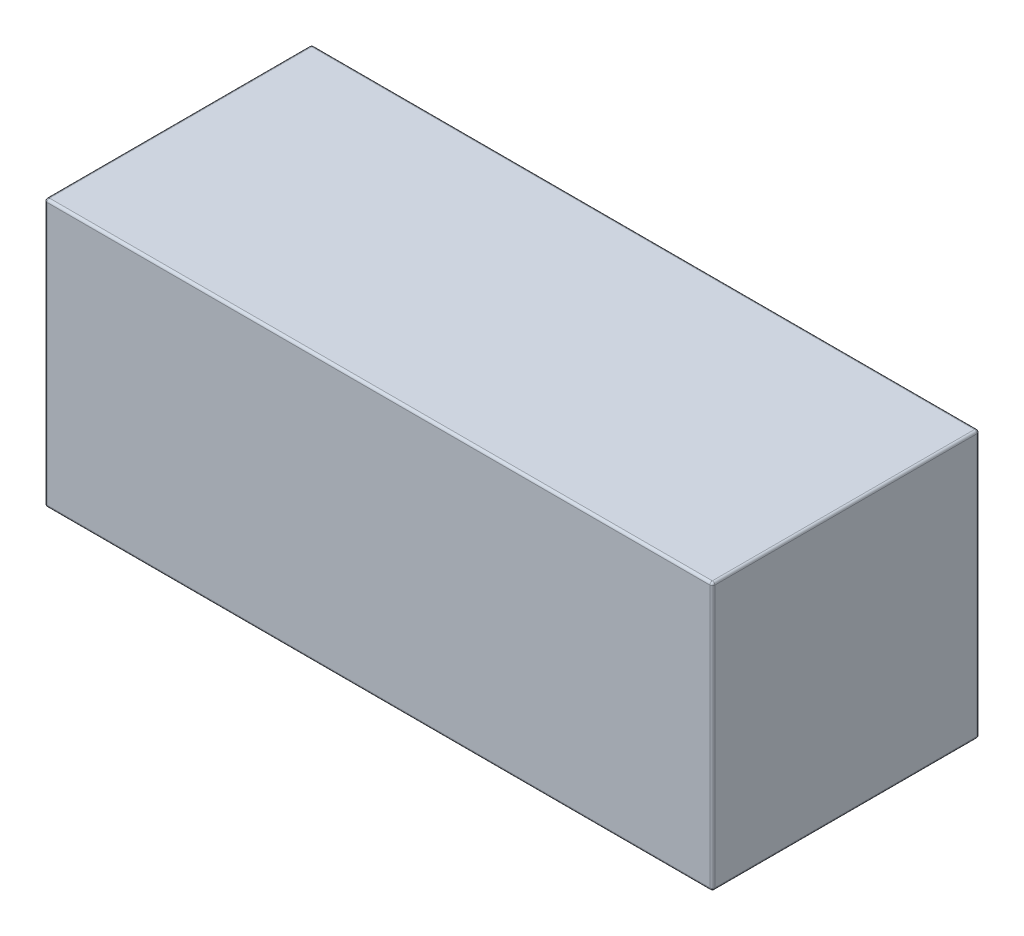
SolidWorks part; units mm, degrees
ref_plane "Plan de face" through (0, 0, 0) normal (0, 0, 1) x (1, 0, 0)
ref_plane "Plan de dessus" through (0, 0, 0) normal (0, 1, 0) x (1, 0, 0)
ref_plane "Plan de droite" through (0, 0, 0) normal (1, 0, 0) x (0, 0, -1)
sketch "Esquisse1" plane through (0, 0, 0) normal (0, 0, 1) x (1, 0, 0)
  line L1 (0, 0) -> (135, 0)
  line L2 (0, 0) -> (0, -54)
  line L3 (0, -54) -> (135, -54)
  line L4 (135, 0) -> (135, -54)
  dimension "D1" = 135
  dimension "D2" = 54
extrude "Boss.-Extru.1" add sketch "Esquisse1" along normal blind 54
sketch "Esquisse2" plane through (0, -54, 0) normal (0, -1, 0) x (1, 0, 0)
  line L0 (135, 54) -> (135, 0) construction
  line L1 (62.25, 51) -> (72.75, 51)
  line L2 (62.25, 51) -> (62.25, 40.5)
  line L3 (62.25, 40.5) -> (72.75, 40.5)
  line L4 (72.75, 51) -> (72.75, 40.5)
  line L5 (0, 54) -> (135, 54) construction
  line L13 (78, 32.25) -> (88.5, 32.25)
  line L14 (78, 32.25) -> (78, 21.75)
  line L15 (78, 21.75) -> (88.5, 21.75)
  line L16 (88.5, 32.25) -> (88.5, 21.75)
  point P4 (88.5, 27)
  point P7 (135, 27)
  point P8 (67.5, 51)
  point P11 (67.5, 54)
  dimension "D1" = 10.5
  dimension "D2" = 10.5
  dimension "D3" = 10.5
  dimension "D4" = 10.5
  dimension "D5" = 0
  dimension "D6" = 0
  dimension "D7" = 13.5
  dimension "D8" = 10.5
extrude "Enlèv. mat.-Extru.1" cut sketch "Esquisse2" against normal blind 4.5
ref_plane "Plan1" through (0, 0, 27) normal (0, 0, 1) x (1, 0, 0)
ref_plane "Plan2" through (67.5, 0, 0) normal (1, 0, 0) x (0, 0, -1)
ref_plane "Plan3" through (47.25, 0, 47.25) normal (0.7071, 0, 0.7071) x (0.7071, 0, -0.7071)
fillet "Congé1" radius 0.5 12 edges at (0, -54, 27) (67.5, -54, 54) (0, -27, 54) (135, -54, 27) (135, -27, 54) (67.5, -54, 0) (135, -27, 0) (0, -27, 0) (135, 0, 27) (67.5, 0, 54) (0, 0, 27) (67.5, 0, 0)
mirror "Symétrie1" about plane through (67.5, 0, 0) normal (1, 0, 0) of "Enlèv. mat.-Extru.1"
mirror "Symétrie2" about plane through (0, 0, 27) normal (0, 0, 1) of "Symétrie1"
